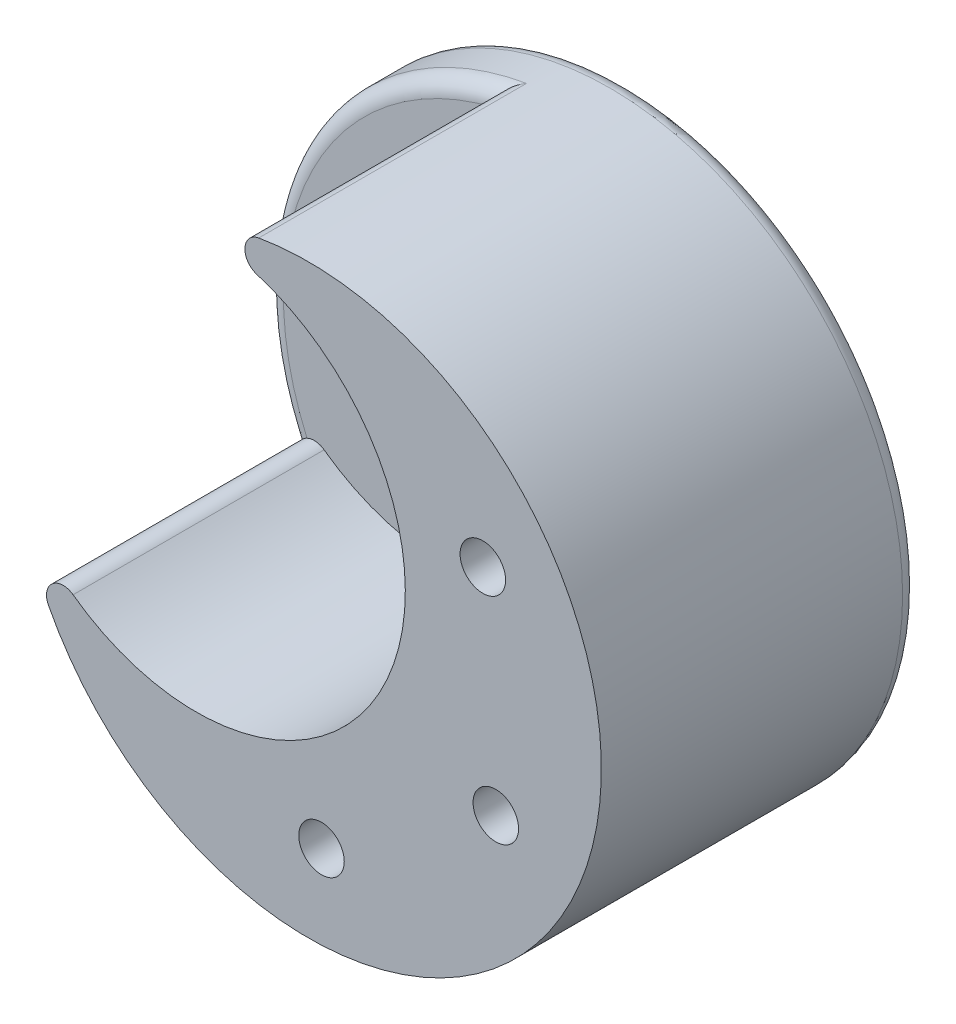
SolidWorks part; units mm, degrees
ref_plane "Front Plane" through (0, 0, 0) normal (0, 0, 1) x (1, 0, 0)
ref_plane "Top Plane" through (0, 0, 0) normal (0, 1, 0) x (1, 0, 0)
ref_plane "Right Plane" through (0, 0, 0) normal (1, 0, 0) x (0, 0, -1)
sketch "Sketch1" plane through (0, 0, 0) normal (0, 0, 1) x (1, 0, 0)
  line L0 (0, 0) -> (28.4284, -14.1382) construction
  circle A0 centre (0, 0) radius 7.62
  circle A2 centre (8.5285, -4.2415) radius 22.225
  arc A3 (-9.932, -30.1566) -> (18.0544, 26.1171) centre (0, 0) ccw construction
  circle A4 centre (0, 0) radius 11 construction
  point P9 (28.4284, -14.1382)
  dimension "D1" = 15.24
  dimension "D2" = 9.525
extrude "Boss-Extrude1" add sketch "Sketch1" along normal blind 5.08
ref_plane "Plane1" through (0, 0, 0) normal (0.4453, 0.8954, 0) x (0.8954, -0.4453, 0)
sketch "Sketch2" plane through (0, 0, 5.08) normal (0, 0, 1) x (1, 0, 0)
  circle A0 centre (8.5285, -4.2415) radius 22.225 construction
  arc A1 (-13.2291, -8.7753) -> (-0.9851, 15.8444) centre (8.5285, -4.2415) ccw
  arc A3 (-13.2291, -8.7753) -> (-0.9851, 15.8444) centre (0, 0) ccw
  dimension "D1" = 31.75
extrude "Boss-Extrude2" add sketch "Sketch2" along normal up to surface (19.0501 mm away)
fillet "Fillet1" radius 1.27 4 edges at (-11.3714, 5.6553, 5.08) (30.7535, -4.2415, 0) (-13.2291, -8.7753, 14.605) (-0.9851, 15.8444, 14.605)
hole_wizard "#8-32 Tapped Hole1" positions "Sketch3" profile "Sketch4" tap size "#8-32" standard "ANSI Inch"
sketch "Sketch3" plane through (0, 0, 24.1301) normal (0, 0, 1) x (1, 0, 0)
  point P0 (21.7576, 4.5339)
  point P3 (22.7427, -11.3106)
  point P6 (9.5136, -20.0859)
sketch "Sketch4" plane through (21.7576, 4.5339, 24.1301) normal (1, 0, 0) x (0, -1, 0)
  line L0 (0, 0) -> (0, 13.7378)
  line L1 (0, 13.7378) -> (1.7272, 12.7)
  line L2 (1.7272, 12.7) -> (1.7272, 0)
  line L5 (1.7272, 0) -> (0, 0)
  line L10 (0, 13.7378) -> (-1.7272, 12.7) construction
  line L11 (0, -6.35) -> (0, 107.95) construction
  dimension "Tap Drill Dia." = 3.4544
  dimension "Tap Drill Depth" = 12.7
  dimension "Drill Angle" = 118
cosmetic thread "Hole Thread1" parameters "D1"=8.382, "D2"=4.1656
cosmetic thread "Hole Thread2" parameters "D1"=8.382, "D2"=4.1656
cosmetic thread "Hole Thread3" parameters "D1"=8.382, "D2"=4.1656
